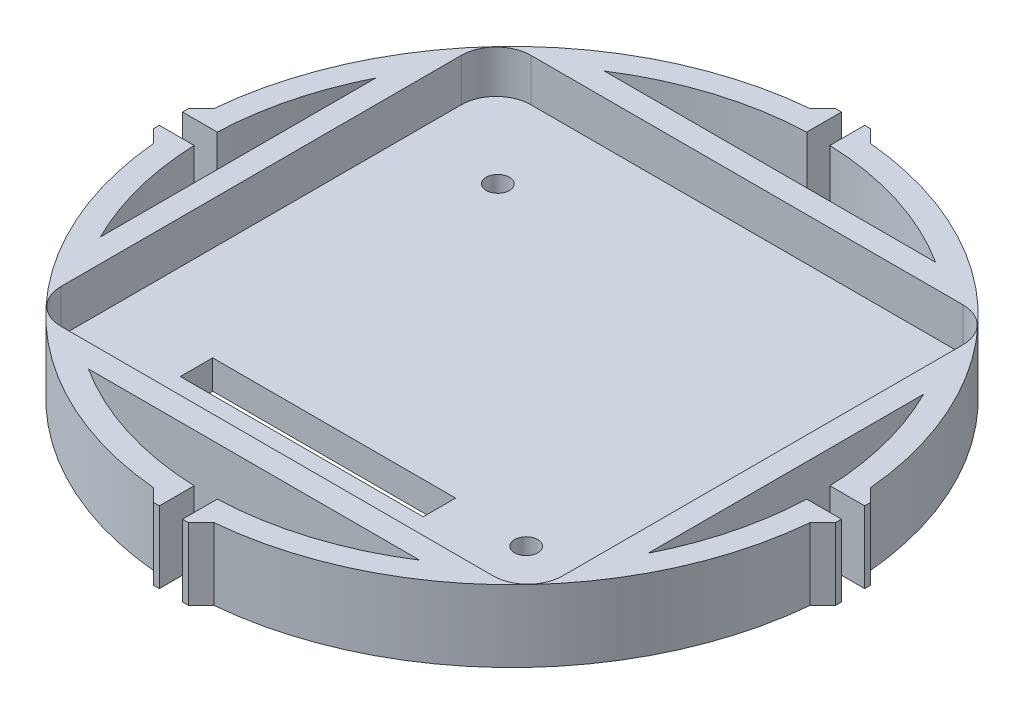
SolidWorks part; units mm, degrees
ref_plane "Front Plane" through (0, 0, 0) normal (0, 0, 1) x (1, 0, 0)
ref_plane "Top Plane" through (0, 0, 0) normal (0, 1, 0) x (1, 0, 0)
ref_plane "Right Plane" through (0, 0, 0) normal (1, 0, 0) x (0, 0, -1)
sketch "Sketch1" plane through (0, 0, 0) normal (0, 1, 0) x (1, 0, 0)
  circle A0 centre (0, 0) radius 28.5
  dimension "D1" = 57
extrude "Boss-Extrude1" add sketch "Sketch1" along normal blind 6.2
sketch "Sketch2" plane through (0, 6.2, 0) normal (0, 1, 0) x (1, 0, 0)
  line L0 (0, 28.5) -> (0, -28.5) construction
  line L1 (-21.675, 20.3) -> (21.675, 20.3)
  line L2 (-21.675, 20.3) -> (-21.675, -20.3)
  line L3 (-21.675, -20.3) -> (21.675, -20.3)
  line L4 (21.675, 20.3) -> (21.675, -20.3)
  line L5 (-21.675, 20.3) -> (21.675, -20.3) construction
  line L6 (-21.675, -20.3) -> (21.675, 20.3) construction
  line L7 (-28.5, 0) -> (28.5, 0) construction
  circle A0 centre (-18.675, 17.3) radius 3
  circle A1 centre (0, 0) radius 28.5 construction
  circle A2 centre (18.675, 17.3) radius 3
  circle A3 centre (18.675, -17.3) radius 3
  circle A4 centre (-18.675, -17.3) radius 3
  point P0 (0, 0)
  dimension "D3" = 6
  dimension "D1" = 43.35
  dimension "D2" = 40.6
extrude "Cut-Extrude1" cut sketch "Sketch2" against normal blind 3.7 contours L2 A4 L3 A3 L4 A2 L1 A0 | A0 | A2 | A3 | A4 region at (0, 6.2, 0) region at (-18.675, 6.2, -17.3) region at (18.675, 6.2, -17.3) region at (-18.675, 6.2, 17.3) region at (18.675, 6.2, 17.3)
sketch "Sketch3" plane through (0, 2.5, 0) normal (0, 1, 0) x (1, 0, 0)
  line L0 (-21.675, -13.8) -> (21.675, -13.8) construction
  line L1 (-21.675, 17.3) -> (-21.675, -17.3) construction
  line L2 (21.675, 17.3) -> (21.675, -17.3) construction
  line L3 (-21.675, 17.3) -> (-21.675, -17.3) construction
  line L4 (-13.475, -12.4) -> (7.525, -12.4)
  line L5 (-13.475, -12.4) -> (-13.475, -15.2)
  line L6 (-13.475, -15.2) -> (7.525, -15.2)
  line L7 (7.525, -12.4) -> (7.525, -15.2)
  line L8 (-13.475, -12.4) -> (7.525, -15.2) construction
  line L9 (-13.475, -15.2) -> (7.525, -12.4) construction
  line L10 (-18.675, -20.3) -> (18.675, -20.3) construction
  line L11 (-18.675, 20.3) -> (18.675, 20.3) construction
  line L12 (-28.5, 0) -> (28.5, 0) construction
  line L13 (0, 28.5) -> (0, -28.5) construction
  line L14 (0, 0) -> (19.2228, 21.0412) construction
  line L15 (-14.175, 12.95) -> (0, 0) construction
  circle A0 centre (-14.175, 12.95) radius 1
  circle A1 centre (0, 0) radius 28.5 construction
  circle A2 centre (14.175, -12.95) radius 1
  point P6 (-2.975, -13.8)
  dimension "D5" = 2
  dimension "D1" = 8.2
  dimension "D2" = 21
  dimension "D3" = 2.8
  dimension "D4" = 5.1
  dimension "D6" = 7.5
  dimension "D7" = 7.35
extrude "Cut-Extrude2" cut sketch "Sketch3" against normal up to next contours A0 | L7 L4 L5 L6 | A2 region at (-2.975, 2.5, 13.8) region at (-14.175, 2.5, -12.95) region at (14.175, 2.5, 12.95)
sketch "Sketch4" plane through (0, 6.2, 0) normal (0, 1, 0) x (1, 0, 0)
  line L0 (0, 20.3) -> (0, 22.3) construction
  line L1 (-28.5, 1) -> (28.5, 1)
  line L2 (-28.5, 1) -> (-28.5, -1)
  line L3 (-28.5, -1) -> (28.5, -1)
  line L4 (28.5, 1) -> (28.5, -1)
  line L5 (-28.5, 1) -> (28.5, -1) construction
  line L6 (-28.5, -1) -> (28.5, 1) construction
  line L7 (-1, -28.5) -> (1, -28.5)
  line L8 (-1, -28.5) -> (-1, 28.5)
  line L9 (-1, 28.5) -> (1, 28.5)
  line L10 (1, -28.5) -> (1, 28.5)
  line L11 (-1, -28.5) -> (1, 28.5) construction
  line L12 (-1, 28.5) -> (1, -28.5) construction
  line L13 (23.675, -22.3) -> (-23.675, -22.3)
  line L14 (23.675, -22.3) -> (23.675, 22.3)
  line L15 (23.675, 22.3) -> (-23.675, 22.3)
  line L16 (-23.675, -22.3) -> (-23.675, 22.3)
  line L17 (23.675, -22.3) -> (-23.675, 22.3) construction
  line L18 (23.675, 22.3) -> (-23.675, -22.3) construction
  line L19 (-18.675, 20.3) -> (18.675, 20.3) construction
  line L20 (-23.675, 0) -> (-21.675, 0) construction
  line L21 (-21.675, 17.3) -> (-21.675, -17.3) construction
  line L22 (-26.5, 0) -> (-28.5, 0) construction
  circle A0 centre (0, 0) radius 28.5 construction
  circle A1 centre (0, 0) radius 26.5
  point P0 (0, 0)
  circle M6 centre (0, 0) radius 28.5
  dimension "D1" = 2
extrude "Cut-Extrude3" cut sketch "Sketch4" against normal up to next contours L8 A1 L15 | L15 A1 L10 | A1 L10 L8 M6 | L10 A1 L8 L15 | A1 L1 L3 M6 | L1 A1 L3 L16 | L16 A1 L1 | L3 A1 L16 | L13 A1 L8 | L10 A1 L13 | L8 A1 L10 L13 | A1 L8 L10 M6 | L1 A1 L14 | L14 A1 L3 | L3 A1 L1 L14 | A1 L3 L1 M6 region at (-27.4939, 6.2, 0) region at (-24.7714, 6.2, -5.0659) region at (-25.0844, 6.2, 0) region at (-24.7714, 6.2, 5.0659) region at (-5.9957, 6.2, -23.9455) region at (0, 6.2, -27.4939) region at (0, 6.2, -24.3969) region at (-5.9957, 6.2, 23.9455) region at (0, 6.2, 27.4939) region at (24.7714, 6.2, -5.0659) region at (25.0844, 6.2, 0) region at (5.9957, 6.2, -23.9455) region at (0, 6.2, 24.3969) region at (27.4939, 6.2, 0) region at (24.7714, 6.2, 5.0659) region at (5.9957, 6.2, 23.9455)
sketch "Sketch5" plane through (0, 6.2, 0) normal (0, 1, 0) x (1, 0, 0)
  line L0 (-1, 28.4825) -> (-1, 29.4825)
  line L1 (-1, 29.4825) -> (-1.5, 29.4825)
  line L2 (-1.5, 29.4825) -> (-2.6014, 28.381)
  line L3 (0, 28.5) -> (0, -28.5) construction
  line L4 (-28.5, 0) -> (28.5, 0) construction
  line L5 (-20.1525, -20.1525) -> (20.1525, 20.1525) construction
  line L6 (1, 28.4825) -> (1, 29.4825)
  line L7 (1, 29.4825) -> (1.5, 29.4825)
  line L8 (1.5, 29.4825) -> (2.6014, 28.381)
  line L9 (1.5, -29.4825) -> (2.6014, -28.381)
  line L10 (1, -29.4825) -> (1.5, -29.4825)
  line L11 (1, -28.4825) -> (1, -29.4825)
  line L12 (-1, -28.4825) -> (-1, -29.4825)
  line L13 (-1, -29.4825) -> (-1.5, -29.4825)
  line L14 (-1.5, -29.4825) -> (-2.6014, -28.381)
  line L15 (29.4825, 1.5) -> (28.381, 2.6014)
  line L16 (29.4825, 1) -> (29.4825, 1.5)
  line L17 (28.4825, 1) -> (29.4825, 1)
  line L18 (29.4825, -1) -> (29.4825, -1.5)
  line L19 (28.4825, -1) -> (29.4825, -1)
  line L20 (29.4825, -1.5) -> (28.381, -2.6014)
  line L21 (-29.4825, 1.5) -> (-28.381, 2.6014)
  line L22 (-29.4825, 1) -> (-29.4825, 1.5)
  line L23 (-28.4825, 1) -> (-29.4825, 1)
  line L24 (-29.4825, -1.5) -> (-28.381, -2.6014)
  line L25 (-29.4825, -1) -> (-29.4825, -1.5)
  line L26 (-28.4825, -1) -> (-29.4825, -1)
  arc A1 (-1, 28.4825) -> (-28.4825, 1) centre (0, 0) ccw construction
  circle A2 centre (0, 0) radius 28.5
  arc M5 (-28.4825, -1) -> (-1, -28.4825) centre (0, 0) ccw
  arc M11 (1, -28.4825) -> (28.4825, -1) centre (0, 0) ccw
  arc M17 (28.4825, 1) -> (1, 28.4825) centre (0, 0) ccw
  arc M23 (-1, 28.4825) -> (-28.4825, 1) centre (0, 0) ccw
  dimension "D1" = 0.5
  dimension "D2" = 1
  dimension "D3" = 135
  dimension "D4" = 45
extrude "Boss-Extrude2" add sketch "Sketch5" against normal up to surface (6.2 mm away) contours L1 L2 L0 M23 | L8 L7 L6 M17 | L17 L16 L15 M17 | L20 L18 L19 M11 | L26 L25 L24 M5 | L23 L21 L22 M23 | L14 L13 L12 M5 | L11 L10 L9 M11 region at (-1.5739, 6.2, -28.8722) region at (1.5739, 6.2, -28.8722) region at (-28.8722, 6.2, -1.5739) region at (28.8722, 6.2, -1.5739) region at (-28.8722, 6.2, 1.5739) region at (28.8722, 6.2, 1.5739) region at (-1.5739, 6.2, 28.8722) region at (1.5739, 6.2, 28.8722) up to face at (-2.975, 0, 13.8)
